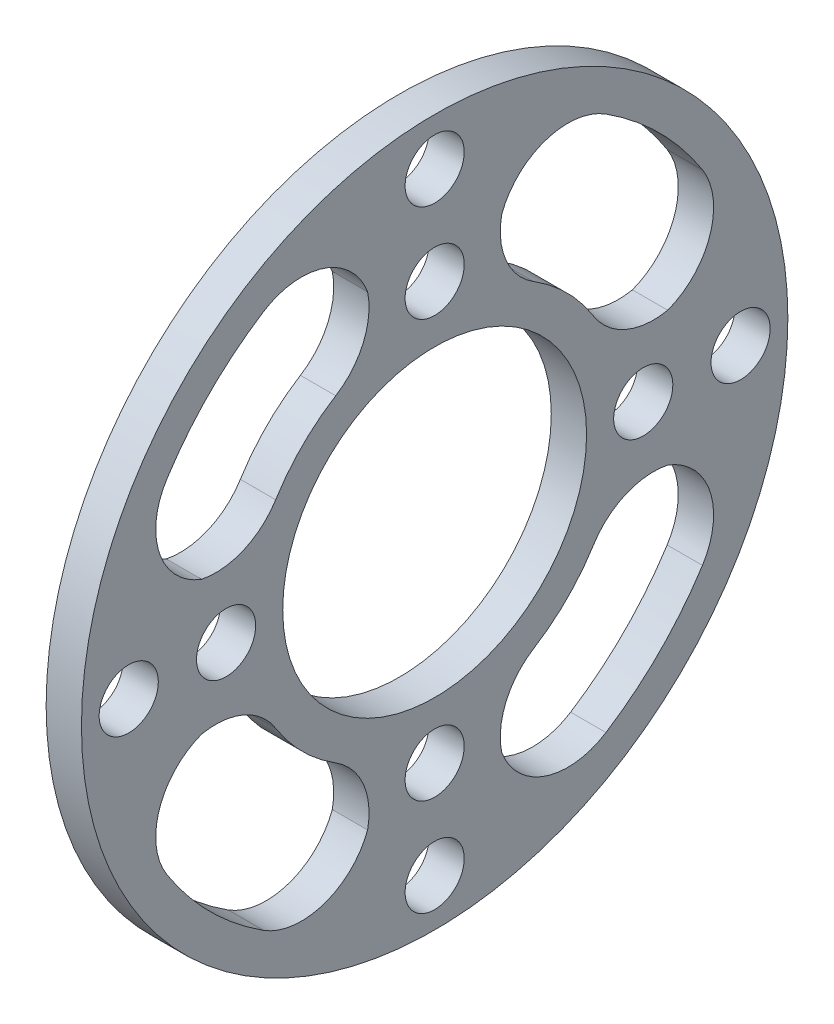
SolidWorks part; units mm, degrees
ref_plane "Front Plane" through (0, 0, 0) normal (0, 0, 1) x (1, 0, 0)
ref_plane "Top Plane" through (0, 0, 0) normal (0, 1, 0) x (1, 0, 0)
ref_plane "Right Plane" through (0, 0, 0) normal (1, 0, 0) x (0, 0, -1)
sketch "Sketch1" plane through (0, 0, 0) normal (1, 0, 0) x (0, 0, -1)
  line L0 (0, 22) -> (0, 0) construction
  line L1 (12.9443, 3.7117) -> (21.9744, 6.3011)
  line L2 (0, 0) -> (15, 0) construction
  line L3 (0, 0) -> (-25.4, 0) construction
  line L4 (-12.9443, 3.7117) -> (-21.9744, 6.3011)
  line L5 (-3.7117, 12.9443) -> (-6.3011, 21.9744)
  line L6 (3.7117, 12.9443) -> (6.3011, 21.9744)
  line L7 (3.7117, -12.9443) -> (6.3011, -21.9744)
  line L8 (12.9443, -3.7117) -> (21.9744, -6.3011)
  line L9 (-12.9443, -3.7117) -> (-21.9744, -6.3011)
  line L10 (-3.7117, -12.9443) -> (-6.3011, -21.9744)
  circle A0 centre (0, 22) radius 2.127
  circle A3 centre (15, 0) radius 2.127
  circle A8 centre (15, 0) radius 2
  circle A10 centre (22, 0) radius 2.127
  circle A11 centre (0, -22) radius 2.127
  circle A12 centre (-22, 0) radius 2.127
  circle A13 centre (0, -15) radius 2.127
  circle A14 centre (-15, 0) radius 2.127
  circle A15 centre (0, 15) radius 2.127
  circle A16 centre (0, 0) radius 25.4
  circle A17 centre (0, 0) radius 10.926
  arc A20 (-6.3011, 21.9744) -> (-21.9744, 6.3011) centre (0, 0) ccw
  arc A21 (-3.7117, 12.9443) -> (-12.9443, 3.7117) centre (0, 0) ccw
  circle A22 centre (0, 0) radius 10.926
  arc A23 (21.9744, 6.3011) -> (6.3011, 21.9744) centre (0, 0) ccw
  arc A24 (12.9443, 3.7117) -> (3.7117, 12.9443) centre (0, 0) ccw
  circle A25 centre (0, 0) radius 10.926
  arc A26 (6.3011, -21.9744) -> (21.9744, -6.3011) centre (0, 0) ccw
  arc A27 (3.7117, -12.9443) -> (12.9443, -3.7117) centre (0, 0) ccw
  circle A28 centre (0, 0) radius 10.926
  arc A29 (-21.9744, -6.3011) -> (-6.3011, -21.9744) centre (0, 0) ccw
  arc A30 (-12.9443, -3.7117) -> (-3.7117, -12.9443) centre (0, 0) ccw
  point P3 (0, 0)
  point P6 (0, 0)
  point P16 (0, 0)
  point P24 (0, 0)
  point P29 (-22.4028, 6.4239)
  point P30 (-6.4239, 22.4028)
  point P49 (0, 0)
  dimension "D3" = 4.254
  dimension "D4" = 4.254
  dimension "D5" = 4
  dimension "D6" = 4
  dimension "D7" = 50.8
  dimension "D8" = 21.852
  dimension "D11" = 2.54
  dimension "D1" = 22
  dimension "D2" = 15
  dimension "D9" = 4
  dimension "D10" = 16
extrude "Boss-Extrude1" add sketch "Sketch1" along normal blind 2.54 contours A16 A17 A0 A3 A10 A11 A12 A13 A14 A15 region at (0, 0, 24.6816)
fillet "Fillet1" radius 5.08 16 edges at (1.27, 6.3011, -21.9744) (1.27, 3.7117, -12.9443) (1.27, 12.9443, -3.7117) (1.27, 21.9744, -6.3011) (1.27, -6.3011, -21.9744) (1.27, -21.9744, -6.3011) (1.27, -3.7117, -12.9443) (1.27, -12.9443, -3.7117) (1.27, -12.9443, 3.7117) (1.27, -3.7117, 12.9443) (1.27, -6.3011, 21.9744) (1.27, -21.9744, 6.3011) (1.27, 12.9443, 3.7117) (1.27, 3.7117, 12.9443) (1.27, 6.3011, 21.9744) (1.27, 21.9744, 6.3011)
